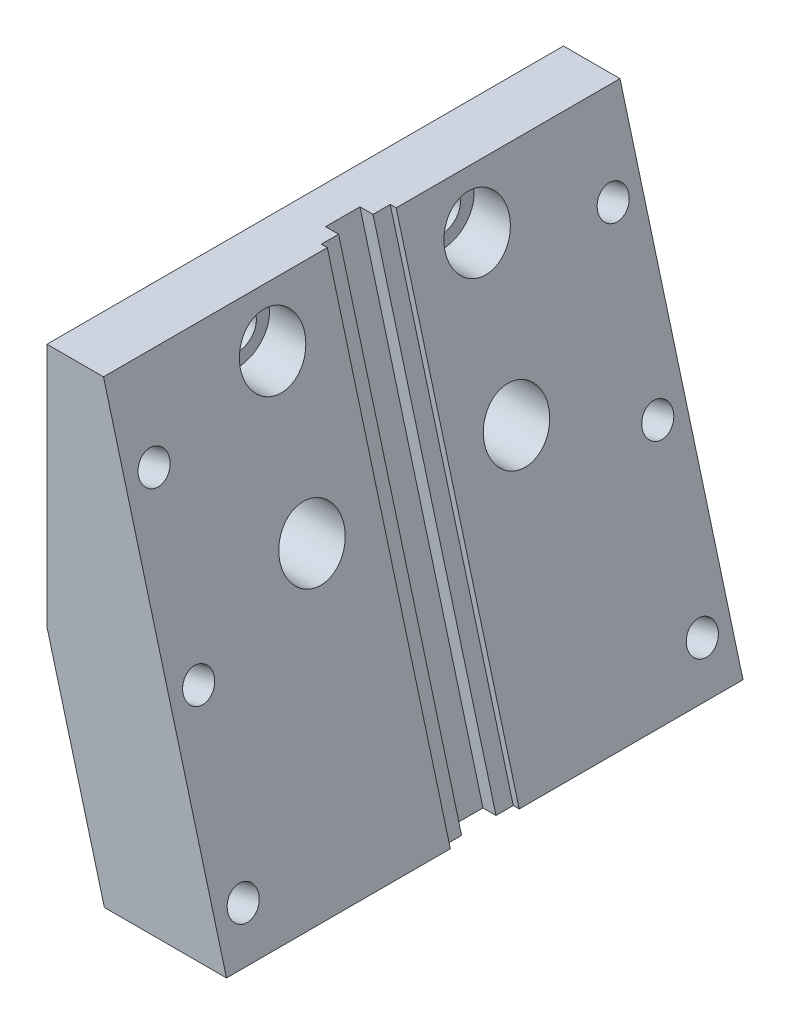
SolidWorks part; units mm, degrees
material "Plain Carbon Steel"
ref_plane "Front Plane" through (0, 0, 0) normal (0, 0, 1) x (1, 0, 0)
ref_plane "Top Plane" through (0, 0, 0) normal (0, 1, 0) x (1, 0, 0)
ref_plane "Right Plane" through (0, 0, 0) normal (1, 0, 0) x (0, 0, -1)
sketch "Sketch1" plane through (0, 0, 0) normal (0, 1, 0) x (1, 0, 0)
  line L1 (-10.5, -22.5) -> (10.5, -22.5)
  line L2 (-10.5, -22.5) -> (-10.5, 22.5)
  line L3 (-10.5, 22.5) -> (10.5, 22.5)
  line L4 (10.5, -22.5) -> (10.5, 22.5)
  line L5 (-10.5, -22.5) -> (10.5, 22.5) construction
  line L6 (-10.5, 22.5) -> (10.5, -22.5) construction
  point P0 (0, 0)
  dimension "D1" = 21
  dimension "D2" = 45
extrude "Boss-Extrude1" add sketch "Sketch1" against normal blind 40
chamfer "Chamfer1" distance 60 angle 15 1 edges at (10.5, 0, 0) first distance on face at (10.5, -20, 0)
sketch "Sketch2" plane through (-5.2034, -1.3942, 0) normal (0.9659, 0.2588, 0) x (0, 0, -1)
  line L0 (0, 1.4434) -> (0, -39.9676) construction
  line L1 (-22.5, 1.4434) -> (22.5, 1.4434) construction
  line L2 (-22.5, -39.9676) -> (22.5, -39.9676) construction
  line L4 (-1.5, -41.7621) -> (1.5, -41.7621)
  line L5 (-1.5, -41.7621) -> (-1.5, 3.2379)
  line L6 (-1.5, 3.2379) -> (1.5, 3.2379)
  line L7 (1.5, -41.7621) -> (1.5, 3.2379)
  line L8 (-1.5, -41.7621) -> (1.5, 3.2379) construction
  line L9 (-1.5, 3.2379) -> (1.5, -41.7621) construction
  point P6 (0, -19.2621)
  dimension "D1" = 3
  dimension "D2" = 45
extrude "Cut-Extrude1" cut sketch "Sketch2" against normal blind 1.6
sketch "Sketch3" plane through (-5.2034, -1.3942, 0) normal (0.9659, 0.2588, 0) x (0, 0, -1)
  line L0 (0, -1.1501) -> (0, -42.5193) construction
  point P0 (20, -20.9302)
  point P4 (0, -21.8347)
  point P5 (-20, -20.9302)
  dimension "D1" = 20
hole_wizard "#6-32 Tapped Hole1" positions "Sketch4" profile "Sketch5" tap size "#6-32" standard "ANSI Inch"
sketch "Sketch4" plane through (-5.2034, -1.3942, 0) normal (0.9659, 0.2588, 0) x (0, 0, -1)
  point P0 (-20, -20.9302)
  point P3 (20, -20.9302)
  point P6 (-20, -5.9302)
  point P8 (-20, -35.9302)
  point P10 (20, -35.9302)
  point P12 (20, -5.9302)
  dimension "D1" = 15
  dimension "D2" = 15
  dimension "D3" = 15
  dimension "D4" = 15
sketch "Sketch5" plane through (0.2138, -21.6113, 20) normal (0, 0, 1) x (-0.2588, 0.9659, 0)
  line L0 (0, 0) -> (0, 9.8127)
  line L1 (0, 9.8127) -> (1.3525, 9)
  line L2 (1.3525, 9) -> (1.3525, 0)
  line L5 (1.3525, 0) -> (0, 0)
  line L10 (0, 9.8127) -> (-1.3526, 9) construction
  line L11 (0, -6.35) -> (0, 107.95) construction
  dimension "Tap Drill Dia." = 2.7051
  dimension "Tap Drill Depth" = 9
  dimension "Drill Angle" = 118
cosmetic thread "Hole Thread1" parameters "D1"=6.5, "D2"=3.5052
cosmetic thread "Hole Thread2" parameters "D1"=6.5, "D2"=3.5052
cosmetic thread "Hole Thread3" parameters "D1"=6.5, "D2"=3.5052
cosmetic thread "Hole Thread4" parameters "D1"=6.5, "D2"=3.5052
cosmetic thread "Hole Thread5" parameters "D1"=6.5, "D2"=3.5052
cosmetic thread "Hole Thread6" parameters "D1"=6.5, "D2"=3.5052
chamfer "Chamfer2" distance 5 angle 75 1 edges at (-10.5, -40, 0) first distance on face at (0.8167, -40, 0)
sketch "Sketch11" plane through (-10.5, 29.282, 0) normal (1, 0, 0) x (0, 0, 1)
  line L0 (0, 29.282) -> (0, 50.6218) construction
  line L1 (-22.5, 50.6218) -> (22.5, 50.6218) construction
  line L2 (-22.5, 39.9519) -> (22.5, 39.9519) construction
  line L3 (-22.5, 50.6218) -> (-22.5, 29.282) construction
  line L4 (22.5, 50.6218) -> (22.5, 29.282) construction
  circle A0 centre (8.89, 33.5519) radius 1.6319
  circle A1 centre (8.89, 46.3519) radius 1.6319
  circle A2 centre (-8.89, 46.3519) radius 1.6319
  circle A3 centre (-8.89, 33.5519) radius 1.6319
  point P11 (8.89, 46.3519)
  point P12 (-8.89, 46.3519)
  point P13 (8.89, 33.5519)
  point P14 (-8.89, 33.5519)
  dimension "D3" = 3.2639
  dimension "D1" = 8.89
  dimension "D2" = 6.4
extrude "Cut-Extrude3" cut sketch "Sketch11" along normal blind 10
sketch3d "3DSketch1"
  line L1 (-7.5, 0, 0) -> (-7.5, -21.3432, 0) construction
  line L2 (-7.5, -10.6716, 0) -> (-7.5, -10.6716, 22.3444) construction
  circle A0 centre (-7.5, -4.2699, -8.91) radius 2.794
  circle A1 centre (-10.5, -17.0699, -8.89) radius 1.632 construction
  circle A2 centre (-10.5, -4.2699, 8.89) radius 1.632 construction
  circle A3 centre (-7.5, -4.2699, 8.91) radius 2.794
  circle A4 centre (-7.5, -17.0734, 8.91) radius 2.794
  circle A5 centre (-7.5, -17.0734, -8.91) radius 2.794
  point P2 (-10.294, -4.2699, -8.91)
  point P8 (-8.868, -17.0699, -8.89)
  point P9 (-7.5, -17.0699, -8.89)
  point P12 (-8.868, -4.2699, 8.89)
  point P13 (-7.5, -4.2699, 8.89)
  point P16 (-10.294, -4.2699, 8.91)
  point P19 (-10.294, -17.0734, 8.91)
  point P24 (-10.294, -17.0734, -8.91)
  dimension "D2" = 5.588
  dimension "D3" = 12.8
  dimension "D1" = 3
  dimension "D4" = 17.8
extrude "Cut-Extrude4" cut sketch "3DSketch1" along direction (1, 0, 0) on the side against the normal blind 8
sketch "Sketch12" plane through (-5.2034, -1.3942, 0) normal (0.9659, 0.2588, 0) x (0, 0, -1)
  line L1 (-3, -42.7032) -> (3, -42.7032)
  line L2 (-3, -42.7032) -> (-3, 2.2968)
  line L3 (-3, 2.2968) -> (3, 2.2968)
  line L4 (3, -42.7032) -> (3, 2.2968)
  line L5 (-3, -42.7032) -> (3, 2.2968) construction
  line L6 (-3, 2.2968) -> (3, -42.7032) construction
  line L7 (0, -1.1501) -> (0, -42.5193) construction
  point P0 (0, -20.2032)
  dimension "D1" = 6
  dimension "D2" = 45
extrude "Cut-Extrude5" cut sketch "Sketch12" against normal blind 0.5
